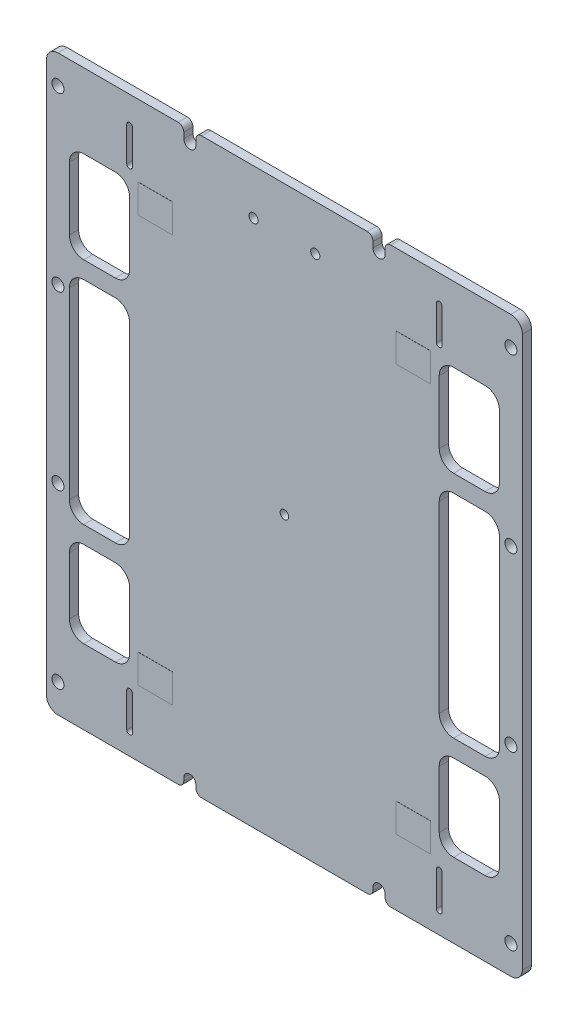
SolidWorks part; units mm, degrees
material "FR4_stuffedProtoboard"
ref_plane "Front Plane" through (0, 0, 0) normal (0, 0, 1) x (1, 0, 0)
ref_plane "Top Plane" through (0, 0, 0) normal (0, 1, 0) x (1, 0, 0)
ref_plane "Right Plane" through (0, 0, 0) normal (1, 0, 0) x (0, 0, -1)
sketch "Sketch1" plane through (0, 0, 0) normal (0, 0, 1) x (1, 0, 0)
  line L1 (-39.5, -50) -> (39.5, -50)
  line L2 (-41.5, -48) -> (-41.5, 48)
  line L3 (-39.5, 50) -> (39.5, 50)
  line L4 (41.5, -48) -> (41.5, 48)
  line L5 (-41.5, -50) -> (41.5, 50) construction
  line L6 (-41.5, 50) -> (41.5, -50) construction
  arc A0 (-39.5, -50) -> (-41.5, -48) centre (-39.5, -48) cw
  arc A1 (39.5, -50) -> (41.5, -48) centre (39.5, -48) ccw
  arc A2 (39.5, 50) -> (41.5, 48) centre (39.5, 48) cw
  arc A3 (-41.5, 48) -> (-39.5, 50) centre (-39.5, 48) cw
  point P0 (0, 0)
  dimension "D3" = 2
  dimension "D1" = 100
  dimension "D2" = 83
extrude "boardOutline" add sketch "Sketch1" along normal blind 1.6
sketch "Sketch2" plane through (0, 0, 1.6) normal (0, 0, 1) x (1, 0, 0)
  line L0 (39.5, 50) -> (-39.5, 50) construction
  line L1 (-41.5, 48) -> (-41.5, -48) construction
  line L2 (-5.385, 42.1) -> (5.385, 42.1) construction
  line L3 (-38, 44.2) -> (-38, 4.2) construction
  line L4 (0, 42.1) -> (0, 50) construction
  circle A0 centre (0, 0) radius 0.75
  circle A1 centre (-38, 44.2) radius 1.05 construction
  circle A2 centre (37.5, 44.2) radius 1.05 construction
  circle A3 centre (37.5, 4.2) radius 1.05 construction
  circle A4 centre (37.5, -35.8) radius 1.05 construction
  circle A5 centre (-38, 4.2) radius 1.05 construction
  circle A6 centre (-38, -35.8) radius 1.05 construction
  circle A7 centre (-5.385, 42.1) radius 0.8
  circle A8 centre (5.385, 42.1) radius 0.8
  dimension "D1" = 1.5
  dimension "D2" = 2.1
  dimension "D9" = 10.77
  dimension "D7" = 1.6
  dimension "D11" = 7.9
  dimension "D3" = 5.8
  dimension "D4" = 3.5
  dimension "D8" = 40
  dimension "D10" = 37.5
  dimension "D5" = 2
  dimension "D6" = 3
extrude "componentHoles" cut sketch "Sketch2" against normal through all
sketch "Sketch4" plane through (0, 0, 1.6) normal (0, 0, 1) x (1, 0, 0)
  line L0 (-27, 39.25) -> (-27, 45.25) construction
  line L1 (-27.5, 39.25) -> (-27.5, 45.25)
  line L2 (-26.5, 39.25) -> (-26.5, 45.25)
  line L3 (39.5, 50) -> (-39.5, 50) construction
  line L4 (-41.5, 48) -> (-41.5, -48) construction
  line L5 (27, 39.25) -> (27, 45.25) construction
  line L6 (26.5, 39.25) -> (26.5, 45.25)
  line L7 (27.5, 39.25) -> (27.5, 45.25)
  line L8 (27, -46.25) -> (27, -40.25) construction
  line L9 (26.5, -46.25) -> (26.5, -40.25)
  line L10 (27.5, -46.25) -> (27.5, -40.25)
  line L11 (-27, -46.25) -> (-27, -40.25) construction
  line L12 (-27.5, -46.25) -> (-27.5, -40.25)
  line L13 (-26.5, -46.25) -> (-26.5, -40.25)
  line L14 (-27, 39.25) -> (27, 39.25) construction
  line L15 (0, 39.25) -> (0, 50) construction
  arc A0 (-27.5, 39.25) -> (-26.5, 39.25) centre (-27, 39.25) ccw
  arc A1 (-26.5, 45.25) -> (-27.5, 45.25) centre (-27, 45.25) ccw
  arc A2 (26.5, 39.25) -> (27.5, 39.25) centre (27, 39.25) ccw
  arc A3 (27.5, 45.25) -> (26.5, 45.25) centre (27, 45.25) ccw
  arc A4 (26.5, -46.25) -> (27.5, -46.25) centre (27, -46.25) ccw
  arc A5 (27.5, -40.25) -> (26.5, -40.25) centre (27, -40.25) ccw
  arc A6 (-27.5, -46.25) -> (-26.5, -46.25) centre (-27, -46.25) ccw
  arc A7 (-26.5, -40.25) -> (-27.5, -40.25) centre (-27, -40.25) ccw
  point P2 (-27, 42.25)
  point P16 (27, 42.25)
  point P23 (27, -43.25)
  point P30 (-27, -43.25)
  dimension "D1" = 4.75
  dimension "D2" = 14
  dimension "D3" = 1
  dimension "D4" = 6
  dimension "D7" = 54
  dimension "D9" = 79.5
  dimension "D5" = 2
  dimension "D6" = 2
extrude "solarCellContactHoles" cut sketch "Sketch4" against normal blind 1.6
sketch "FrameLattice" plane through (0, 0, 0) normal (0, 0, 1) x (1, 0, 0)
  line L0 (5, 45) -> (-5, 45) construction
  line L1 (5, 45) -> (-5, 45)
  line L2 (-7.5, 41.5) -> (-7.5, 42.5) construction
  line L3 (-7.5, 41.5) -> (-7.5, 42.5)
  line L4 (-12.5, -19) -> (12.5, -19)
  line L5 (15, -16.5) -> (15, 15.5)
  line L6 (12.5, 18) -> (-12.5, 18)
  line L7 (-15, 15.5) -> (-15, -16.5)
  line L8 (-12.5, -19) -> (12.5, -19)
  line L9 (15, -16.5) -> (15, 15.5)
  line L10 (12.5, 18) -> (-12.5, 18)
  line L11 (-15, 15.5) -> (-15, -16.5)
  line L15 (7.5, 42.5) -> (7.5, 41.5) construction
  line L21 (7.5, 42.5) -> (7.5, 41.5)
  line L22 (5, 39) -> (-5, 39) construction
  line L23 (5, 39) -> (-5, 39)
  line L28 (7, 40) -> (-7, 40)
  line L92 (-35, -19) -> (-20.5, -19)
  line L93 (-18, -16.5) -> (-18, 15.5)
  line L94 (-20.5, 18) -> (-35, 18)
  line L95 (-37.5, 15.5) -> (-37.5, -16.5)
  line L96 (-35, -19) -> (-20.5, -19)
  line L97 (-18, -16.5) -> (-18, 15.5)
  line L98 (-20.5, 18) -> (-35, 18)
  line L99 (-37.5, 15.5) -> (-37.5, -16.5)
  line L100 (20.5, -47) -> (35, -47)
  line L101 (37.5, -44.5) -> (37.5, -24.5)
  line L102 (35, -22) -> (20.5, -22)
  line L103 (18, -24.5) -> (18, -44.5)
  line L104 (20.5, -47) -> (35, -47)
  line L105 (37.5, -44.5) -> (37.5, -24.5)
  line L106 (35, -22) -> (20.5, -22)
  line L107 (18, -24.5) -> (18, -44.5)
  line L108 (-12.5, -47) -> (12.5, -47)
  line L109 (15, -44.5) -> (15, -24.5)
  line L110 (12.5, -22) -> (-12.5, -22)
  line L111 (-15, -24.5) -> (-15, -44.5)
  line L112 (-12.5, -47) -> (12.5, -47)
  line L113 (15, -44.5) -> (15, -24.5)
  line L114 (12.5, -22) -> (-12.5, -22)
  line L115 (-15, -24.5) -> (-15, -44.5)
  line L116 (-35, -47) -> (-20.5, -47)
  line L117 (-18, -44.5) -> (-18, -24.5)
  line L118 (-20.5, -22) -> (-35, -22)
  line L119 (-37.5, -24.5) -> (-37.5, -44.5)
  line L120 (-35, -47) -> (-20.5, -47)
  line L121 (-18, -44.5) -> (-18, -24.5)
  line L122 (-20.5, -22) -> (-35, -22)
  line L123 (-37.5, -24.5) -> (-37.5, -44.5)
  line L124 (20.5, -19) -> (35, -19)
  line L125 (37.5, -16.5) -> (37.5, 15.5)
  line L126 (35, 18) -> (20.5, 18)
  line L127 (18, 15.5) -> (18, -16.5)
  line L128 (20.5, -19) -> (35, -19)
  line L129 (37.5, -16.5) -> (37.5, 15.5)
  line L130 (35, 18) -> (20.5, 18)
  line L131 (18, 15.5) -> (18, -16.5)
  line L132 (-35, 21) -> (-20.5, 21)
  line L133 (-18, 23.5) -> (-18, 43.5)
  line L134 (-20.5, 46) -> (-35, 46)
  line L135 (-37.5, 43.5) -> (-37.5, 23.5)
  line L136 (-35, 21) -> (-20.5, 21)
  line L137 (-18, 23.5) -> (-18, 43.5)
  line L138 (-20.5, 46) -> (-35, 46)
  line L139 (-37.5, 43.5) -> (-37.5, 23.5)
  line L140 (-12.5, 21) -> (12.5, 21)
  line L141 (15, 23.5) -> (15, 43.5)
  line L142 (12.5, 46) -> (-12.5, 46)
  line L143 (-15, 43.5) -> (-15, 23.5)
  line L144 (-12.5, 21) -> (12.5, 21)
  line L145 (15, 23.5) -> (15, 43.5)
  line L147 (-15, 43.5) -> (-15, 23.5)
  line L148 (20.5, 21) -> (35, 21)
  line L149 (37.5, 23.5) -> (37.5, 43.5)
  line L150 (35, 46) -> (20.5, 46)
  line L151 (18, 43.5) -> (18, 23.5)
  line L152 (20.5, 21) -> (35, 21)
  line L153 (37.5, 23.5) -> (37.5, 43.5)
  line L154 (35, 46) -> (20.5, 46)
  line L155 (18, 43.5) -> (18, 23.5)
  line L213 (12.5, 46) -> (-12.5, 46)
  arc A1 (7.5, 42.5) -> (5, 45) centre (5, 42.5) ccw construction
  circle A2 centre (-16.5, 48) radius 0.8
  circle A3 centre (-16.5, 48) radius 0.8
  arc A4 (7.5, 42.5) -> (5, 45) centre (5, 42.5) ccw
  arc A5 (12.5, -19) -> (15, -16.5) centre (12.5, -16.5) ccw
  arc A6 (15, 15.5) -> (12.5, 18) centre (12.5, 15.5) ccw
  arc A7 (-12.5, 18) -> (-15, 15.5) centre (-12.5, 15.5) ccw
  arc A8 (-15, -16.5) -> (-12.5, -19) centre (-12.5, -16.5) ccw
  arc A9 (12.5, -19) -> (15, -16.5) centre (12.5, -16.5) ccw
  arc A10 (15, 15.5) -> (12.5, 18) centre (12.5, 15.5) ccw
  arc A11 (-12.5, 18) -> (-15, 15.5) centre (-12.5, 15.5) ccw
  arc A12 (-15, -16.5) -> (-12.5, -19) centre (-12.5, -16.5) ccw
  arc A13 (-5, 45) -> (-7.5, 42.5) centre (-5, 42.5) ccw construction
  arc A14 (-5, 45) -> (-7.5, 42.5) centre (-5, 42.5) ccw
  arc A15 (-7.5, 41.5) -> (-5, 39) centre (-5, 41.5) ccw construction
  arc A16 (-7.5, 41.5) -> (-5, 39) centre (-5, 41.5) ccw
  arc A21 (7, 40) -> (7.5, 41.5) centre (5, 41.5) ccw construction
  arc A22 (7, 40) -> (7.5, 41.5) centre (5, 41.5) ccw
  arc A23 (5, 39) -> (7.5, 41.5) centre (5, 41.5) ccw construction
  arc A24 (5, 39) -> (7.5, 41.5) centre (5, 41.5) ccw
  circle A92 centre (39.5, -15) radius 0.8
  circle A93 centre (39.5, -15) radius 0.8
  circle A94 centre (39.5, 15) radius 0.8
  arc A119 (-20.5, -19) -> (-18, -16.5) centre (-20.5, -16.5) ccw
  arc A120 (-18, 15.5) -> (-20.5, 18) centre (-20.5, 15.5) ccw
  arc A121 (-35, 18) -> (-37.5, 15.5) centre (-35, 15.5) ccw
  arc A122 (-37.5, -16.5) -> (-35, -19) centre (-35, -16.5) ccw
  arc A123 (-20.5, -19) -> (-18, -16.5) centre (-20.5, -16.5) ccw
  arc A124 (-18, 15.5) -> (-20.5, 18) centre (-20.5, 15.5) ccw
  arc A125 (-35, 18) -> (-37.5, 15.5) centre (-35, 15.5) ccw
  arc A126 (-37.5, -16.5) -> (-35, -19) centre (-35, -16.5) ccw
  arc A127 (35, -47) -> (37.5, -44.5) centre (35, -44.5) ccw
  arc A128 (37.5, -24.5) -> (35, -22) centre (35, -24.5) ccw
  arc A129 (20.5, -22) -> (18, -24.5) centre (20.5, -24.5) ccw
  arc A130 (18, -44.5) -> (20.5, -47) centre (20.5, -44.5) ccw
  arc A131 (35, -47) -> (37.5, -44.5) centre (35, -44.5) ccw
  arc A132 (37.5, -24.5) -> (35, -22) centre (35, -24.5) ccw
  arc A133 (20.5, -22) -> (18, -24.5) centre (20.5, -24.5) ccw
  arc A134 (18, -44.5) -> (20.5, -47) centre (20.5, -44.5) ccw
  arc A135 (12.5, -47) -> (15, -44.5) centre (12.5, -44.5) ccw
  arc A136 (15, -24.5) -> (12.5, -22) centre (12.5, -24.5) ccw
  arc A137 (-12.5, -22) -> (-15, -24.5) centre (-12.5, -24.5) ccw
  arc A138 (-15, -44.5) -> (-12.5, -47) centre (-12.5, -44.5) ccw
  arc A139 (12.5, -47) -> (15, -44.5) centre (12.5, -44.5) ccw
  arc A140 (15, -24.5) -> (12.5, -22) centre (12.5, -24.5) ccw
  arc A141 (-12.5, -22) -> (-15, -24.5) centre (-12.5, -24.5) ccw
  arc A142 (-15, -44.5) -> (-12.5, -47) centre (-12.5, -44.5) ccw
  arc A143 (-20.5, -47) -> (-18, -44.5) centre (-20.5, -44.5) ccw
  arc A144 (-18, -24.5) -> (-20.5, -22) centre (-20.5, -24.5) ccw
  arc A145 (-35, -22) -> (-37.5, -24.5) centre (-35, -24.5) ccw
  arc A146 (-37.5, -44.5) -> (-35, -47) centre (-35, -44.5) ccw
  arc A147 (-20.5, -47) -> (-18, -44.5) centre (-20.5, -44.5) ccw
  arc A148 (-18, -24.5) -> (-20.5, -22) centre (-20.5, -24.5) ccw
  arc A149 (-35, -22) -> (-37.5, -24.5) centre (-35, -24.5) ccw
  arc A150 (-37.5, -44.5) -> (-35, -47) centre (-35, -44.5) ccw
  arc A151 (35, -19) -> (37.5, -16.5) centre (35, -16.5) ccw
  arc A152 (37.5, 15.5) -> (35, 18) centre (35, 15.5) ccw
  arc A153 (20.5, 18) -> (18, 15.5) centre (20.5, 15.5) ccw
  arc A154 (18, -16.5) -> (20.5, -19) centre (20.5, -16.5) ccw
  arc A155 (35, -19) -> (37.5, -16.5) centre (35, -16.5) ccw
  arc A156 (37.5, 15.5) -> (35, 18) centre (35, 15.5) ccw
  arc A157 (20.5, 18) -> (18, 15.5) centre (20.5, 15.5) ccw
  arc A158 (18, -16.5) -> (20.5, -19) centre (20.5, -16.5) ccw
  arc A159 (-20.5, 21) -> (-18, 23.5) centre (-20.5, 23.5) ccw
  arc A160 (-18, 43.5) -> (-20.5, 46) centre (-20.5, 43.5) ccw
  arc A161 (-35, 46) -> (-37.5, 43.5) centre (-35, 43.5) ccw
  arc A162 (-37.5, 23.5) -> (-35, 21) centre (-35, 23.5) ccw
  arc A163 (-20.5, 21) -> (-18, 23.5) centre (-20.5, 23.5) ccw
  arc A164 (-18, 43.5) -> (-20.5, 46) centre (-20.5, 43.5) ccw
  arc A165 (-35, 46) -> (-37.5, 43.5) centre (-35, 43.5) ccw
  arc A166 (-37.5, 23.5) -> (-35, 21) centre (-35, 23.5) ccw
  arc A167 (12.5, 21) -> (15, 23.5) centre (12.5, 23.5) ccw
  arc A168 (15, 43.5) -> (12.5, 46) centre (12.5, 43.5) ccw
  arc A169 (-12.5, 46) -> (-15, 43.5) centre (-12.5, 43.5) ccw
  arc A170 (-15, 23.5) -> (-12.5, 21) centre (-12.5, 23.5) ccw
  arc A171 (12.5, 21) -> (15, 23.5) centre (12.5, 23.5) ccw
  arc A172 (15, 43.5) -> (12.5, 46) centre (12.5, 43.5) ccw
  arc A173 (-12.5, 46) -> (-15, 43.5) centre (-12.5, 43.5) ccw
  arc A174 (-15, 23.5) -> (-12.5, 21) centre (-12.5, 23.5) ccw
  arc A175 (35, 21) -> (37.5, 23.5) centre (35, 23.5) ccw
  arc A176 (37.5, 43.5) -> (35, 46) centre (35, 43.5) ccw
  arc A177 (20.5, 46) -> (18, 43.5) centre (20.5, 43.5) ccw
  arc A178 (18, 23.5) -> (20.5, 21) centre (20.5, 23.5) ccw
  arc A179 (35, 21) -> (37.5, 23.5) centre (35, 23.5) ccw
  arc A180 (37.5, 43.5) -> (35, 46) centre (35, 43.5) ccw
  arc A181 (20.5, 46) -> (18, 43.5) centre (20.5, 43.5) ccw
  arc A182 (18, 23.5) -> (20.5, 21) centre (20.5, 23.5) ccw
  circle A183 centre (39.5, 15) radius 0.8
  circle A184 centre (-39.5, 45) radius 0.8
  circle A185 centre (-39.5, 45) radius 0.8
  circle A186 centre (39.5, 45) radius 0.8
  circle A187 centre (39.5, 45) radius 0.8
  circle A188 centre (-39.5, 15) radius 0.8
  circle A189 centre (-39.5, 15) radius 0.8
  circle A190 centre (16.5, -48.5) radius 0.8
  circle A191 centre (16.5, -48.5) radius 0.8
  circle A192 centre (-16.5, -48.5) radius 0.8
  circle A193 centre (-16.5, -48.5) radius 0.8
  circle A194 centre (16.5, 48) radius 0.8
  circle A195 centre (16.5, 48) radius 0.8
  circle A196 centre (-39.5, -15) radius 0.8
  circle A197 centre (-39.5, -15) radius 0.8
  circle A216 centre (39.5, -45) radius 0.8
  circle A217 centre (39.5, -45) radius 0.8
  circle A218 centre (-39.5, -45) radius 0.8
  circle A235 centre (-39.5, -45) radius 0.8
  dimension "D1" = 0
  dimension "D6" = 14
  dimension "D9" = 0
  dimension "D25" = 0
  dimension "D26" = 0
  dimension "D27" = 0
  dimension "D28" = 0
  dimension "D29" = 0
  dimension "D30" = 0
  dimension "D31" = 0
  dimension "D32" = 0
  dimension "D33" = 0
  dimension "D34" = 0
  dimension "D35" = 0
  dimension "D36" = 0
  dimension "D37" = 0
  dimension "D38" = 0
  dimension "D39" = 0
  dimension "D40" = 0
  dimension "D41" = 0
  dimension "D50" = 0
  dimension "D51" = 0
sketch "Sketch3" plane through (0, 0, 1.6) normal (0, 0, 1) x (1, 0, 0)
  line L0 (-35, -19) -> (-20.5, -19) construction
  line L1 (-35, 37) -> (-29.5, 37)
  line L2 (-37.5, 34.5) -> (-37.5, 23.5)
  line L3 (-35, 21) -> (-29.5, 21)
  line L4 (-27, 34.5) -> (-27, 23.5)
  line L6 (-29.5, -22) -> (-35, -22)
  line L7 (-37.5, 15.5) -> (-37.5, -16.5) construction
  line L8 (-20.5, -22) -> (-35, -22) construction
  line L9 (0, 50) -> (0, -50) construction
  line L10 (39.5, 50) -> (-39.5, 50) construction
  line L11 (-39.5, -50) -> (39.5, -50) construction
  line L12 (-27, -24.5) -> (-27, -34.5)
  line L13 (-29.5, -37) -> (-35, -37)
  line L14 (-37.5, -24.5) -> (-37.5, -34.5)
  line L15 (-20.5, 18) -> (-35, 18) construction
  line L16 (-35, 21) -> (-20.5, 21) construction
  line L19 (-29.5, -19) -> (-35, -19)
  line L25 (-27, -16.5) -> (-27, 15.5)
  line L26 (-29.5, 18) -> (-35, 18)
  line L27 (-37.5, -16.5) -> (-37.5, 15.5)
  arc A0 (-37.5, 23.5) -> (-35, 21) centre (-35, 23.5) ccw
  arc A1 (-29.5, 21) -> (-27, 23.5) centre (-29.5, 23.5) ccw
  arc A2 (-29.5, 37) -> (-27, 34.5) centre (-29.5, 34.5) cw
  arc A3 (-35, 37) -> (-37.5, 34.5) centre (-35, 34.5) ccw
  arc A4 (-29.5, -19) -> (-27, -16.5) centre (-29.5, -16.5) ccw
  arc A5 (-27, -34.5) -> (-29.5, -37) centre (-29.5, -34.5) cw
  arc A6 (-35, -37) -> (-37.5, -34.5) centre (-35, -34.5) cw
  arc A7 (-35, -22) -> (-37.5, -24.5) centre (-35, -24.5) ccw
  arc A8 (-29.5, -22) -> (-27, -24.5) centre (-29.5, -24.5) cw
  arc A9 (-37.5, 23.5) -> (-35, 21) centre (-35, 23.5) ccw construction
  arc A17 (-35, -19) -> (-37.5, -16.5) centre (-35, -16.5) cw
  arc A18 (-35, 18) -> (-37.5, 15.5) centre (-35, 15.5) ccw
  arc A19 (-27, 15.5) -> (-29.5, 18) centre (-29.5, 15.5) ccw
  point P12 (-27, 21)
  point P15 (-27, 37)
  point P18 (-37.5, 37)
  dimension "D10" = 13
  dimension "D1" = 10.5
  dimension "D3" = 13
extrude "windows_1side" cut sketch "Sketch3" against normal through all
sketch "Sketch5" plane through (0, 0, 1.6) normal (0, 0, 1) x (1, 0, 0)
  line L0 (-41.5, 48) -> (-41.5, -48) construction
  line L1 (-25.5, 37.5) -> (-19.5, 37.5)
  line L2 (-25.5, 37.5) -> (-25.5, 32.5)
  line L3 (-25.5, 32.5) -> (-19.5, 32.5)
  line L4 (-19.5, 37.5) -> (-19.5, 32.5)
  line L5 (0, 37.5) -> (0, 50) construction
  line L6 (19.5, 37.5) -> (19.5, 32.5)
  line L7 (25.5, 37.5) -> (25.5, 32.5)
  line L8 (19.5, 32.5) -> (25.5, 32.5)
  line L9 (19.5, 37.5) -> (25.5, 37.5)
  line L10 (19.5, -33.5) -> (19.5, -38.5)
  line L11 (25.5, -33.5) -> (25.5, -38.5)
  line L12 (19.5, -38.5) -> (25.5, -38.5)
  line L13 (19.5, -33.5) -> (25.5, -33.5)
  line L14 (-25.5, -33.5) -> (-25.5, -38.5)
  line L15 (-19.5, -33.5) -> (-19.5, -38.5)
  line L16 (-25.5, -38.5) -> (-19.5, -38.5)
  line L17 (-25.5, -33.5) -> (-19.5, -33.5)
  line L18 (-19.5, 37.5) -> (19.5, 37.5) construction
  line L19 (-25.5, 37.5) -> (-25.5, -33.5) construction
  line L20 (39.5, 50) -> (-39.5, 50) construction
  arc A0 (-27.5, 39.25) -> (-26.5, 39.25) centre (-27, 39.25) ccw construction
  dimension "D1" = 5
  dimension "D2" = 6
  dimension "D3" = 16
  dimension "D4" = 1.75
  dimension "D7" = 45
  dimension "D8" = 71
  dimension "D5" = 2
  dimension "D6" = 2
extrude "contactPads" add sketch "Sketch5" along normal blind 0.02
hole_wizard "M2 Clearance Hole1" positions "Sketch6" profile "Sketch7" hole size "M2" standard "ANSI Metric" end condition through all
sketch "Sketch6" plane through (0, 0, 0) normal (0, 0, -1) x (-1, 0, 0)
  line L5 (39.5, -50) -> (39.5, -45) construction
  line L6 (39.5, -50) -> (-39.5, -50) construction
  line L7 (39.5, -45) -> (39.5, -15) construction
  line L8 (39.5, -15) -> (39.5, 15) construction
  line L9 (39.5, 15) -> (39.5, 45) construction
  line L10 (39.5, 45) -> (39.5, 50) construction
  line L11 (-39.5, 50) -> (39.5, 50) construction
  line L15 (37.5, -27.0602) -> (41.5, -27.0602) construction
  line L16 (37.5, -24.5) -> (37.5, -34.5) construction
  line L17 (41.5, 48) -> (41.5, -48) construction
  point P0 (39.5, 45)
  point P27 (39.5, -15)
  point P36 (39.5, -45)
  point P38 (39.5, 15)
  point P73 (39.5, -27.0602)
  dimension "D2" = 5
sketch "Sketch7" plane through (-39.5, 45, 0) normal (1, 0, 0) x (0, 1, 0)
  line L0 (0, 0) -> (0, 1.62)
  line L1 (0, 1.62) -> (1.05, 1.62)
  line L2 (1.05, 1.62) -> (1.05, 0)
  line L5 (1.05, 0) -> (0, 0)
  line L11 (0, -6.35) -> (0, 107.95) construction
  dimension "Thru Hole Dia." = 2.1
  dimension "Thru Hole Depth" = 1.62
sketch "Sketch10" plane through (0, 0, 0) normal (0, 0, -1) x (-1, 0, 0)
  line L0 (16.5, 48) -> (16.5, 55.0732) construction
  line L1 (15.45, 48) -> (15.45, 55.0732)
  line L2 (17.55, 48) -> (17.55, 55.0732)
  line L3 (16.5, -48.5) -> (16.5, -55.5732) construction
  line L4 (17.55, -48.5) -> (17.55, -55.5732)
  line L5 (15.45, -48.5) -> (15.45, -55.5732)
  line L6 (41.5, 48) -> (41.5, -48) construction
  line L8 (39.5, -50) -> (-39.5, -50) construction
  line L9 (-39.5, 50) -> (39.5, 50) construction
  arc A0 (15.45, 48) -> (17.55, 48) centre (16.5, 48) ccw
  arc A1 (17.55, 55.0732) -> (15.45, 55.0732) centre (16.5, 55.0732) ccw
  arc A2 (17.55, -48.5) -> (15.45, -48.5) centre (16.5, -48.5) ccw
  arc A3 (15.45, -55.5732) -> (17.55, -55.5732) centre (16.5, -55.5732) ccw
  point P2 (16.5, 51.5366)
  point P7 (16.5, -52.0366)
  dimension "D1" = 1.05
  dimension "D2" = 25
  dimension "D3" = 2
  dimension "D4" = 1.5
extrude "Cut-Extrude1" cut sketch "Sketch10" against normal through all both and the other way through all
fillet "Fillet3" radius 1 4 edges at (-17.55, 50, 0.8) (-15.45, 50, 0.8) (-15.45, -50, 0.8) (-17.55, -50, 0.8)
mirror "Mirror1" about plane through (0, 0, 0) normal (1, 0, 0) of "Cut-Extrude1", "Fillet3", "windows_1side", "M2 Clearance Hole1"
sketch "Wedge Fastener Hole Locations" plane through (0, 0, 0) normal (0, 0, -1) x (-1, 0, 0)
  circle A1 centre (22, 5.4) radius 1.2 construction
  circle A2 centre (22, 5.4) radius 1.2
  circle A3 centre (-22, -4.6) radius 1.2 construction
  circle A4 centre (0, -4.6) radius 1.2 construction
  circle A5 centre (22, -4.6) radius 1.2 construction
  circle A6 centre (-22, -4.6) radius 1.2
  circle A7 centre (0, -4.6) radius 1.2
  circle A8 centre (22, -4.6) radius 1.2
  circle A9 centre (0, 25.4) radius 1.2 construction
  circle A10 centre (22, 25.4) radius 1.2 construction
  circle A11 centre (0, 35.4) radius 1.2 construction
  circle A12 centre (22, 35.4) radius 1.2 construction
  circle A13 centre (0, 25.4) radius 1.2
  circle A14 centre (22, 25.4) radius 1.2
  circle A15 centre (0, 35.4) radius 1.2
  circle A16 centre (22, 35.4) radius 1.2
  circle A17 centre (0, 15.4) radius 1.2 construction
  circle A18 centre (22, 15.4) radius 1.2 construction
  circle A19 centre (-22, 25.4) radius 1.2 construction
  circle A20 centre (-22, 35.4) radius 1.2 construction
  circle A21 centre (0, 15.4) radius 1.2
  circle A22 centre (22, 15.4) radius 1.2
  circle A23 centre (-22, 25.4) radius 1.2
  circle A24 centre (-22, 35.4) radius 1.2
  circle A25 centre (-22, 15.4) radius 1.2 construction
  circle A26 centre (-22, 15.4) radius 1.2
  circle A27 centre (-22, 5.4) radius 1.2 construction
  circle A28 centre (0, 5.4) radius 1.2 construction
  circle A29 centre (-22, 5.4) radius 1.2
  circle A30 centre (0, 5.4) radius 1.2
  circle A31 centre (-22, -24.6) radius 1.2 construction
  circle A32 centre (0, -24.6) radius 1.2 construction
  circle A33 centre (22, -24.6) radius 1.2 construction
  circle A34 centre (-22, -14.6) radius 1.2 construction
  circle A35 centre (0, -14.6) radius 1.2 construction
  circle A36 centre (22, -14.6) radius 1.2 construction
  circle A37 centre (-22, -24.6) radius 1.2
  circle A38 centre (0, -24.6) radius 1.2
  circle A39 centre (22, -24.6) radius 1.2
  circle A40 centre (-22, -14.6) radius 1.2
  circle A41 centre (0, -14.6) radius 1.2
  circle A42 centre (22, -14.6) radius 1.2
  circle A43 centre (-22, -34.6) radius 1.2 construction
  circle A44 centre (0, -34.6) radius 1.2 construction
  circle A45 centre (22, -34.6) radius 1.2 construction
  circle A46 centre (-22, -34.6) radius 1.2
  circle A47 centre (0, -34.6) radius 1.2
  circle A48 centre (22, -34.6) radius 1.2
